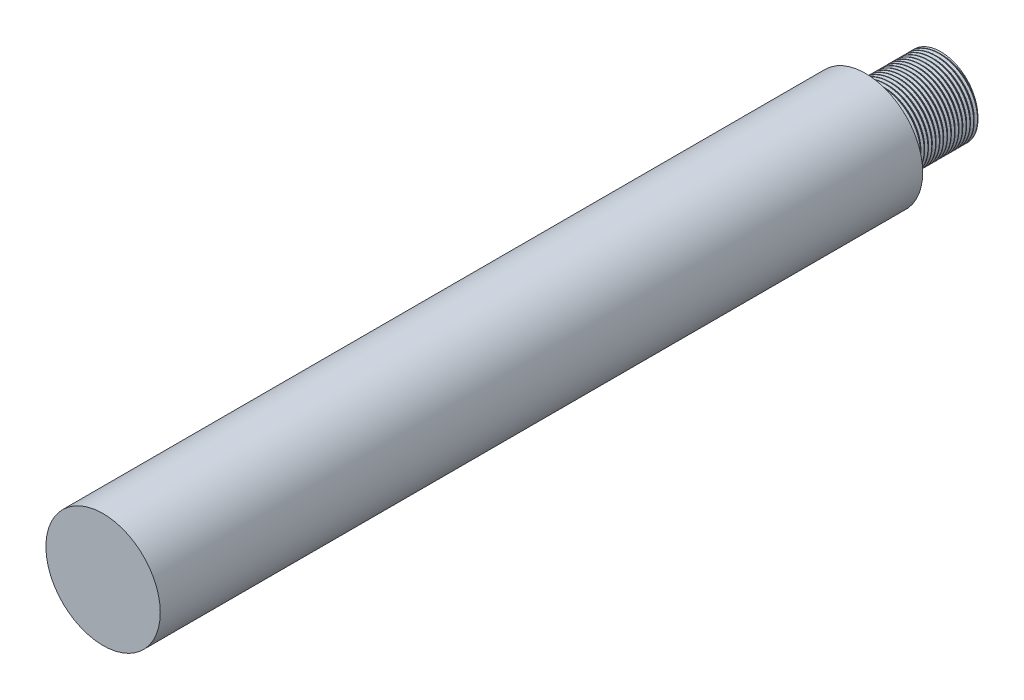
SolidWorks part; units mm, degrees
material "6061-T6 (SS)"
ref_plane "Front Plane" through (0, 0, 0) normal (0, 0, 1) x (1, 0, 0)
ref_plane "Top Plane" through (0, 0, 0) normal (0, 1, 0) x (1, 0, 0)
ref_plane "Right Plane" through (0, 0, 0) normal (1, 0, 0) x (0, 0, -1)
sketch "Sketch2" plane through (0, 0, 0) normal (0, 0, 1) x (1, 0, 0)
  circle A0 centre (0, 0) radius 3.175
extrude "Boss-Extrude1" add sketch "Sketch2" along normal blind 6.35
thread "Thread1" pitch 0.3175 method cut profile "Thread Profile1" start angle 0, offset 0, length 0, pitch 0.3175, diameter 6.35
ref_plane "Plane1" through (-3.175, 0, 6.35) normal (0, -1, 0) x (-1, 0, 0)
sketch "Thread Profile1" plane through (-3.175, 0, 6.35) normal (0, -1, 0) x (-1, 0, 0)
  line L0 (0, 0) -> (0, 0.3175) construction
  line L11 (0, 0) -> (0, 0.2778)
  line L12 (0, 0.2778) -> (-0.1719, 0.1786)
  line L13 (-0.1719, 0.1786) -> (-0.1719, 0.0992)
  line L15 (-0.1719, 0.0992) -> (0, 0)
  line L17 (-0.1719, 0.1389) -> (0, 0.1389) construction
  point P2 (0, 0)
  dimension "Pitch" = 0.3175
  dimension "Profile_Angle" = 60
  dimension "Profile_Land" = 0.0794
  dimension "Profile_Height" = 0.1719
sketch "Sketch5" plane through (0, 0, 6.35) normal (0, 0, 1) x (1, 0, 0)
  circle A0 centre (0, 0) radius 4.7625
  circle A1 centre (0, 0) radius 3.175
  circle A2 centre (0, 0) radius 3.175
  circle M2 centre (0, 0) radius 3.175
  dimension "D2" = 9.525
  dimension "D1" = 0
extrude "Boss-Extrude3" add sketch "Sketch5" along normal blind 63.5 contours M2 | A0 M2 region at (-4.6278, 0, 6.35) region at (0, 0, 6.35)
